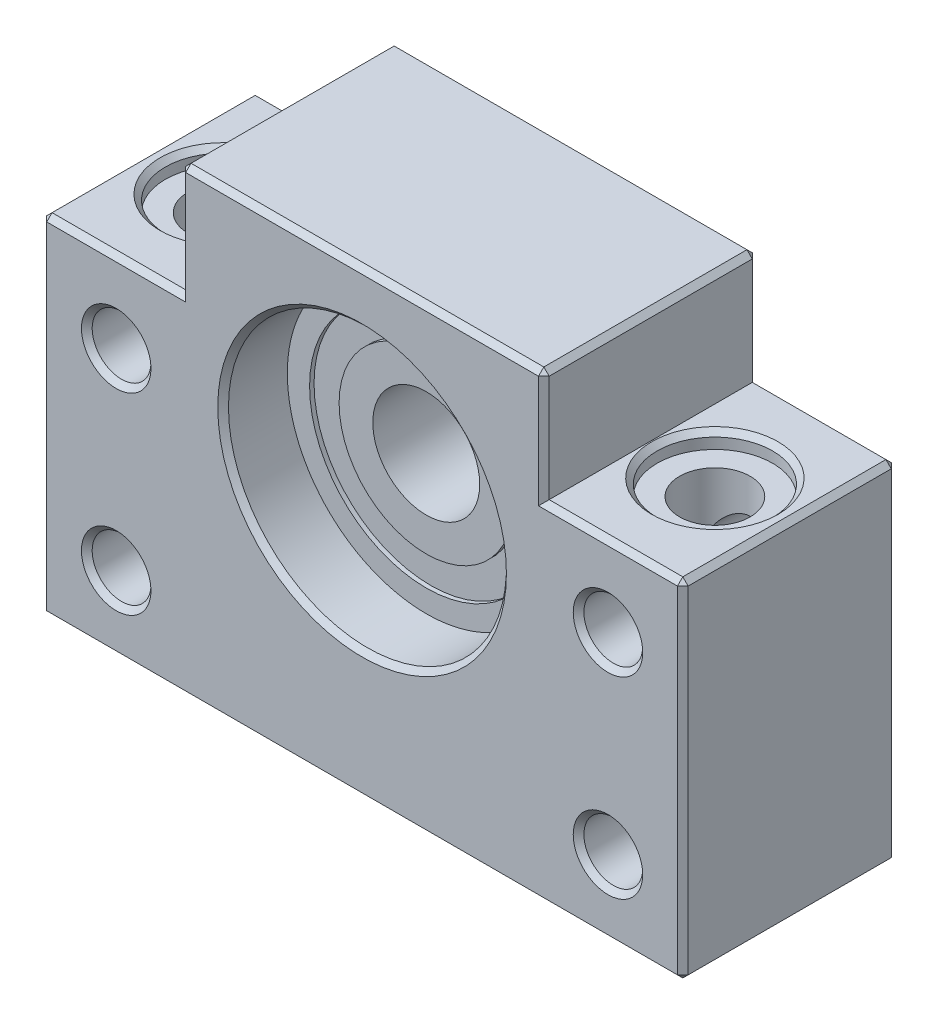
SolidWorks part; units mm, degrees
material "1060 Alloy"
ref_plane "Front Plane" through (0, 0, 0) normal (0, 0, 1) x (1, 0, 0)
ref_plane "Top Plane" through (0, 0, 0) normal (0, 1, 0) x (1, 0, 0)
ref_plane "Right Plane" through (0, 0, 0) normal (1, 0, 0) x (0, 0, -1)
sketch "Sketch1" plane through (0, 0, 0) normal (0, 0, 1) x (1, 0, 0)
  line L0 (0, 25.0042) -> (0, -10.2914) construction
  line L1 (-27.5961, 0) -> (15.5514, 0) construction
  line L2 (17, 18) -> (-17, 18)
  line L3 (-17, 18) -> (-17, 7.5)
  line L4 (-17, 7.5) -> (-30, 7.5)
  line L5 (-30, 7.5) -> (-30, -25)
  line L6 (-30, -25) -> (30, -25)
  line L7 (30, 7.5) -> (30, -25)
  line L8 (17, 7.5) -> (30, 7.5)
  line L9 (17, 18) -> (17, 7.5)
  circle A0 centre (0, 0) radius 13
  point P14 (0, -25)
  point P17 (0, 18)
  dimension "D1" = 26
  dimension "D2" = 18
  dimension "D3" = 25
  dimension "D4" = 32.5
  dimension "D5" = 34
  dimension "D6" = 60
extrude "Boss-Extrude1" add sketch "Sketch1" along normal mid plane 20
sketch "Sketch2" plane through (0, 0, 10) normal (0, 0, 1) x (1, 0, 0)
  line L0 (-23, 0) -> (-23, -18) construction
  line L1 (0, 0) -> (0, -25) construction
  line L2 (-30, -25) -> (30, -25) construction
  circle A0 centre (-23, 0) radius 2.75
  circle A1 centre (-23, -18) radius 2.75
  circle A2 centre (23, -18) radius 2.75
  circle A3 centre (23, 0) radius 2.75
  dimension "D1" = 5.5
  dimension "D2" = 23
  dimension "D3" = 7
  dimension "D4" = 18
extrude "Cut-Extrude1" cut sketch "Sketch2" against normal through all
sketch "Sketch3" plane through (0, 7.5, 0) normal (0, 1, 0) x (1, 0, 0)
  line L0 (0, 0) -> (-23, 0) construction
  line L1 (0, 0) -> (0, 10) construction
  line L2 (17, 10) -> (-17, 10) construction
  circle A0 centre (-23, 0) radius 3.3
  circle A1 centre (23, 0) radius 3.3
  dimension "D1" = 6.6
  dimension "D2" = 23
extrude "Cut-Extrude2" cut sketch "Sketch3" against normal through all
sketch "Sketch4" plane through (0, 7.5, 0) normal (0, 1, 0) x (1, 0, 0)
  circle A0 centre (-23, 0) radius 5.4
  circle A1 centre (23, 0) radius 5.4
  dimension "D1" = 10.8
extrude "Cut-Extrude3" cut sketch "Sketch4" against normal blind 1.5
chamfer "Chamfer1" distance 0.5 angle 45 34 edges at (13, 0, -10) (-20.25, 0, -10) (20.25, 0, -10) (20.25, -18, -10) (-20.25, -18, -10) (13, 0, 10) (30, -25, 0) (30, 7.5, 0) (17, 18, 0) (-17, 18, 0) (-30, 7.5, 0) (-23.5, 7.5, -10) (-30, -8.75, -10) (-17, 12.75, -10) (0, 18, -10) (17, 12.75, -10) (23.5, 7.5, -10) (30, -8.75, -10) (0, -25, -10) (-30, -25, 0) (0, 18, 10) (17, 12.75, 10) (23.5, 7.5, 10) (30, -8.75, 10) (0, -25, 10) (-30, -8.75, 10) (-23.5, 7.5, 10) (-17, 12.75, 10) (-20.25, 0, 10) (20.25, 0, 10) (20.25, -18, 10) (-20.25, -18, 10) (17.6, 7.5, 0) (-28.4, 7.5, 0)
sketch "Sketch5" plane through (0, 0, 0) normal (0, 1, 0) x (1, 0, 0)
  line L1 (-13, 4) -> (-10.9114, 4)
  line L2 (-13, 4) -> (-13, 0)
  line L3 (-13, 0) -> (-5, 0)
  line L4 (-5, 4) -> (-5, 0)
  line L5 (0, 0) -> (-5, 0) construction
  line L6 (-16.5, 10) -> (16.5, 10) construction
  line L7 (-8.1511, 4) -> (-5, 4)
  line L8 (0, 0) -> (0, 10) construction
  line L9 (-10.9114, 4) -> (-10.9114, 3.5824)
  line L10 (-10.9114, 3.5824) -> (-8.1511, 3.5824)
  line L11 (-8.1511, 4) -> (-8.1511, 3.5824)
  line L12 (-13, 9.5) -> (-13, -9.5) construction
  dimension "D1" = 5
  dimension "D2" = 6
revolve "Revolve1" add sketch "Sketch5" angle 360 about L8
mirror "Mirror2" about plane through (-13, 0, 0) normal (0, 0, -1) of bodies 105
